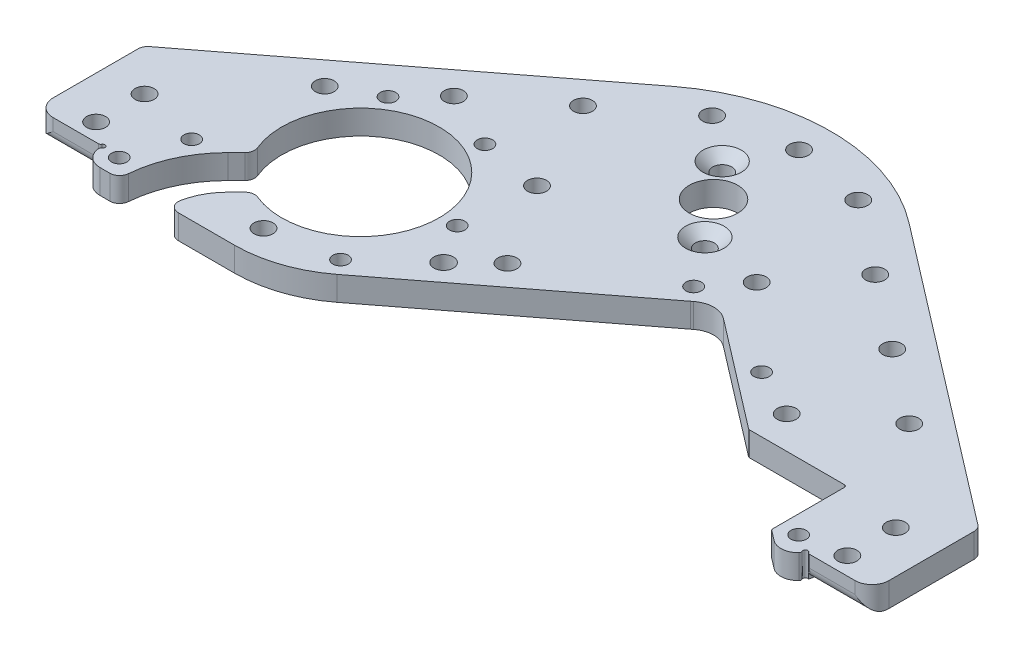
SolidWorks part; units mm, degrees
material "Alum Plate"
ref_plane "Front Plane" through (0, 0, 0) normal (0, 0, 1) x (1, 0, 0)
ref_plane "Top Plane" through (0, 0, 0) normal (0, 1, 0) x (1, 0, 0)
ref_plane "Right Plane" through (0, 0, 0) normal (1, 0, 0) x (0, 0, -1)
sketch "Top Layout" plane through (0, 0, 0) normal (0, 1, 0) x (1, 0, 0)
  line L0 (-114.046, -123.825) -> (-104.775, -123.825) construction
  line L1 (-104.775, -142.875) -> (-101.6, -142.875)
  line L2 (-104.775, -142.875) -> (-104.775, -104.775)
  line L3 (-104.775, -104.775) -> (-101.6, -104.775)
  line L4 (-101.6, -142.875) -> (-101.6, -104.775)
  line L5 (-104.775, -142.875) -> (-101.6, -104.775) construction
  line L6 (-104.775, -104.775) -> (-101.6, -142.875) construction
  line L7 (-19.05, -105.8164) -> (-101.6, -105.8164)
  line L8 (-19.05, -105.8164) -> (-19.05, -141.8336)
  line L9 (-19.05, -141.8336) -> (-101.6, -141.8336)
  line L10 (-101.6, -105.8164) -> (-101.6, -141.8336)
  line L11 (-19.05, -105.8164) -> (-101.6, -141.8336) construction
  line L12 (-19.05, -141.8336) -> (-101.6, -105.8164) construction
  line L13 (-133.096, -85.725) -> (-114.046, -85.725)
  line L14 (-133.096, -85.725) -> (-133.096, -161.925)
  line L15 (-133.096, -161.925) -> (-114.046, -161.925)
  line L16 (-114.046, -85.725) -> (-114.046, -161.925)
  line L17 (-133.096, -85.725) -> (-114.046, -161.925) construction
  line L18 (-133.096, -161.925) -> (-114.046, -85.725) construction
  line L19 (-104.775, -123.825) -> (0, -123.825) construction
  line L20 (0, -123.825) -> (0, 0) construction
  line L21 (-52.3528, -40.1717) -> (0, 0) construction
  line L22 (-70.6449, -16.3328) -> (-18.2922, 23.8388)
  line L23 (-34.0606, -64.0105) -> (18.2922, -23.8388)
  line L24 (-30.9251, 40.3023) -> (-122.2248, -29.7544)
  line L25 (-153.9748, -53.975) -> (-153.9748, -123.825)
  line L26 (-109.5248, -162.052) -> (109.5248, -162.052)
  line L27 (0, -162.052) -> (0, -123.825) construction
  line L28 (-109.5248, -162.052) -> (-109.5248, -20.0093) construction
  line L29 (-104.775, -142.875) -> (-104.775, -152.527)
  line L30 (-104.775, -152.527) -> (104.775, -152.527)
  line L31 (104.775, -104.775) -> (101.6, -104.775)
  line L32 (-144.4498, -73.025) -> (-109.5248, -73.025)
  line L33 (-144.4498, -73.025) -> (-144.4498, -123.825)
  line L34 (-144.4498, -123.825) -> (-109.5248, -123.825) construction
  line L35 (-109.5248, -73.025) -> (-109.5248, -162.052)
  line L36 (-144.4498, -73.025) -> (-109.5248, -123.825) construction
  line L37 (-144.4498, -123.825) -> (-109.5248, -73.025) construction
  line L38 (101.6, -142.875) -> (101.6, -104.775)
  line L39 (104.775, -142.875) -> (101.6, -142.875)
  line L40 (104.775, -142.875) -> (104.775, -104.775)
  line L41 (104.775, -142.875) -> (104.775, -152.527)
  line L42 (109.5248, -162.052) -> (109.5248, -20.0093) construction
  line L43 (30.9251, 40.3023) -> (122.2248, -29.7544)
  line L45 (19.05, -141.8336) -> (101.6, -141.8336)
  line L46 (101.6, -105.8164) -> (101.6, -141.8336)
  line L47 (19.05, -105.8164) -> (101.6, -105.8164)
  line L48 (19.05, -105.8164) -> (19.05, -141.8336)
  line L49 (133.096, -161.925) -> (114.046, -161.925)
  line L50 (114.046, -85.725) -> (114.046, -161.925)
  line L51 (133.096, -85.725) -> (114.046, -85.725)
  line L52 (133.096, -85.725) -> (133.096, -161.925)
  line L53 (144.4498, -123.825) -> (109.5248, -123.825) construction
  line L54 (109.5248, -73.025) -> (109.5248, -162.052)
  line L55 (144.4498, -73.025) -> (109.5248, -73.025)
  line L56 (144.4498, -73.025) -> (144.4498, -123.825)
  line L57 (-109.5248, -123.825) -> (-109.5248, -162.052) construction
  line L62 (-153.9748, -53.975) -> (-122.2248, -53.975)
  line L63 (-122.2248, -53.975) -> (-122.2248, -29.7544)
  line L64 (-144.4498, -123.825) -> (-153.9748, -123.825)
  line L65 (153.9748, -53.975) -> (153.9748, -123.825)
  line L66 (109.5248, -123.825) -> (109.5248, -162.052) construction
  line L67 (144.4498, -123.825) -> (153.9748, -123.825)
  line L68 (122.2248, -29.7544) -> (122.2248, -53.975)
  line L73 (-104.775, -104.775) -> (-104.775, -16.3647) construction
  line L74 (-95.25, -162.052) -> (-95.25, -9.0559) construction
  line L75 (-109.5248, -162.052) -> (-109.5248, -123.825) construction
  line L76 (109.5248, -162.052) -> (109.5248, -123.825) construction
  line L77 (122.2248, -53.975) -> (153.9748, -53.975)
  line L83 (104.775, -155.5496) -> (-104.775, -155.5496) construction
  line L88 (95.25, -162.052) -> (95.25, -9.0559) construction
  line L89 (104.775, -104.775) -> (104.775, -16.3647) construction
  line L92 (-104.775, -152.527) -> (-104.775, -162.052) construction
  line L93 (-14.605, -76.327) -> (14.605, -76.327)
  line L94 (-14.605, -76.327) -> (-14.605, -152.527)
  line L95 (-14.605, -152.527) -> (14.605, -152.527)
  line L96 (14.605, -76.327) -> (14.605, -152.527)
  line L97 (-14.605, -76.327) -> (14.605, -152.527) construction
  line L98 (-14.605, -152.527) -> (14.605, -76.327) construction
  line L99 (104.775, -152.527) -> (104.775, -162.052) construction
  line L100 (-19.05, -105.8164) -> (0, -105.8164) construction
  line L107 (0, -105.8164) -> (19.05, -105.8164) construction
  line L108 (104.775, -123.825) -> (114.046, -123.825) construction
  circle A0 centre (0, 0) radius 114.3
  circle A1 centre (0, 0) radius 6.35
  circle A2 centre (-52.3528, -40.1717) radius 17.8
  circle A3 centre (0, 0) radius 30.0482
  circle A4 centre (-52.3528, -40.1717) radius 30.0482
  arc A5 (-30.9251, 40.3023) -> (30.9251, 40.3023) centre (0, 0) cw
  point P2 (-103.1875, -123.825)
  point P7 (-60.325, -123.825)
  point P12 (-123.571, -123.825)
  point P30 (-126.9873, -98.425)
  point P35 (0, -114.427)
  point P53 (0, -152.527)
  dimension "D1" = 35.6
  dimension "D2" = 12.7
  dimension "D3" = 228.6
  dimension "D11" = 60.0964
  dimension "D12" = 50.8
  dimension "D14" = 52.5
  dimension "D4" = 3.175
  dimension "D5" = 19.05
  dimension "D6" = 76.2
  dimension "D7" = 82.55
  dimension "D8" = 38.1
  dimension "D9" = 104.775
  dimension "D10" = 18.0086
  dimension "D13" = 9.525
  dimension "D15" = 4.7498
  dimension "D16" = 9.525
  dimension "D17" = 9.652
  dimension "D18" = 50.8
  dimension "D19" = 12.446
  dimension "D20" = 65.9892
  dimension "D21" = 19.05
  dimension "D22" = 34.925
  dimension "D23" = 123.825
  dimension "D24" = 12.7
  dimension "D25" = 9.525
  dimension "D26" = 29.21
  dimension "D27" = 76.2
  dimension "D28" = 3.0226
sketch "Side Layout" plane through (0, 0, 0) normal (1, 0, 0) x (0, 0, -1)
  line L0 (0, -38.1) -> (0, 33.7344) construction
  line L1 (-114.3, -20.955) -> (114.3, -20.955)
  line L2 (-114.3, -20.955) -> (-114.3, -33.655)
  line L3 (-114.3, -33.655) -> (114.3, -33.655)
  line L4 (114.3, -20.955) -> (114.3, -33.655)
  line L5 (-114.3, -20.955) -> (114.3, -33.655) construction
  line L6 (-114.3, -33.655) -> (114.3, -20.955) construction
  line L7 (-9.525, -32.9406) -> (9.525, -32.9406)
  line L8 (-9.525, -32.9406) -> (-9.525, -38.1)
  line L9 (-9.525, -38.1) -> (9.525, -38.1)
  line L10 (9.525, -32.9406) -> (9.525, -38.1)
  line L11 (-9.525, -32.9406) -> (9.525, -38.1) construction
  line L12 (-9.525, -38.1) -> (9.525, -32.9406) construction
  line L13 (-11.9126, -29.3338) -> (11.9126, -29.3338)
  line L14 (-11.9126, -29.3338) -> (-11.9126, -32.9406)
  line L15 (-11.9126, -32.9406) -> (11.9126, -32.9406)
  line L16 (11.9126, -29.3338) -> (11.9126, -32.9406)
  line L17 (-11.9126, -29.3338) -> (11.9126, -32.9406) construction
  line L18 (-11.9126, -32.9406) -> (11.9126, -29.3338) construction
  line L19 (-6.35, -32.9406) -> (6.35, -32.9406)
  line L20 (-6.35, -32.9406) -> (-6.35, 33.7344)
  line L21 (-6.35, 33.7344) -> (6.35, 33.7344)
  line L22 (6.35, -32.9406) -> (6.35, 33.7344)
  line L23 (-6.35, -32.9406) -> (6.35, 33.7344) construction
  line L24 (-6.35, 33.7344) -> (6.35, -32.9406) construction
  line L25 (-162.052, 0) -> (-123.825, 0) construction
  line L26 (114.3, -33.655) -> (114.3, 0) construction
  line L27 (-142.875, 19.05) -> (-104.775, 19.05)
  line L28 (-40.1717, -9.525) -> (-40.1717, 5.4) construction
  line L29 (-142.875, 19.05) -> (-142.875, -19.05)
  line L30 (-142.875, -19.05) -> (-104.775, -19.05)
  line L31 (-104.775, 19.05) -> (-104.775, -19.05)
  line L32 (-142.875, 19.05) -> (-104.775, -19.05) construction
  line L33 (-142.875, -19.05) -> (-104.775, 19.05) construction
  line L34 (-130.175, -38.1) -> (-117.9516, -38.1) construction
  line L35 (-57.9717, -14.6) -> (-22.3717, -14.6)
  line L36 (-30.0482, -2.794) -> (30.0482, -2.794)
  line L37 (-30.0482, -2.794) -> (-30.0482, -20.955)
  line L38 (-30.0482, -20.955) -> (30.0482, -20.955)
  line L39 (30.0482, -2.794) -> (30.0482, -20.955)
  line L40 (-30.0482, -2.794) -> (30.0482, -20.955) construction
  line L41 (-30.0482, -20.955) -> (30.0482, -2.794) construction
  line L42 (-30.0482, -2.794) -> (-30.0482, 0) construction
  line L43 (-123.825, 0) -> (0, 0) construction
  line L44 (-57.9717, -14.6) -> (-57.9717, 25.4)
  line L45 (-57.9717, 25.4) -> (-22.3717, 25.4)
  line L46 (-22.3717, -14.6) -> (-22.3717, 25.4)
  line L47 (-19.05, 0) -> (19.05, 0)
  line L48 (-19.05, 0) -> (-19.05, -1.9812)
  line L49 (-19.05, -1.9812) -> (19.05, -1.9812)
  line L50 (19.05, 0) -> (19.05, -1.9812)
  line L51 (-19.05, 0) -> (19.05, -1.9812) construction
  line L52 (-19.05, -1.9812) -> (19.05, 0) construction
  line L53 (-70.2199, -3.175) -> (-10.1235, -3.175)
  line L54 (-70.2199, -3.175) -> (-70.2199, -15.875)
  line L55 (-70.2199, -15.875) -> (-10.1235, -15.875)
  line L56 (-10.1235, -3.175) -> (-10.1235, -15.875)
  line L57 (-70.2199, -3.175) -> (-10.1235, -15.875) construction
  line L58 (-70.2199, -15.875) -> (-10.1235, -3.175) construction
  line L59 (-40.1717, -9.525) -> (-40.1717, 0) construction
  line L60 (-57.9717, -14.6) -> (-22.3717, 25.4) construction
  line L61 (-57.9717, 25.4) -> (-22.3717, -14.6) construction
  line L62 (-22.3717, 0) -> (-57.9717, 0) construction
  line L63 (-137.8162, 0) -> (-123.825, -13.9912) construction
  line L64 (-139.065, 15.24) -> (-108.585, 15.24) construction
  line L65 (-139.065, 15.24) -> (-139.065, -15.24) construction
  line L66 (-139.065, -15.24) -> (-108.585, -15.24) construction
  line L67 (-108.585, 15.24) -> (-108.585, -15.24) construction
  line L68 (-139.065, 15.24) -> (-108.585, -15.24) construction
  line L69 (-139.065, -15.24) -> (-108.585, 15.24) construction
  line L70 (-137.8162, 0) -> (-123.825, 13.9912) construction
  line L71 (-123.825, -13.9912) -> (-109.8338, 0) construction
  line L72 (-123.825, 13.9912) -> (-109.8338, 0) construction
  line L73 (-137.8162, 0) -> (-109.8338, 0) construction
  line L74 (-123.825, -13.9912) -> (-123.825, 13.9912) construction
  line L75 (-6.35, 17.8594) -> (6.35, 17.8594)
  line L76 (114.3, 0) -> (-114.3, 0) construction
  line L77 (-22.3717, 19.05) -> (-6.35, 19.05) construction
  line L78 (-123.825, 38.1) -> (-97.9206, 38.1) construction
  line L79 (-19.05, -3.5814) -> (19.05, -3.5814)
  line L80 (-19.05, -3.5814) -> (-19.05, -1.9812)
  line L81 (-19.05, -1.9812) -> (19.05, -1.9812)
  line L82 (19.05, -3.5814) -> (19.05, -1.9812)
  line L83 (-19.05, -3.5814) -> (19.05, -1.9812) construction
  line L84 (-19.05, -1.9812) -> (19.05, -3.5814) construction
  line L85 (-8.7376, -16.7608) -> (8.7376, -16.7608)
  line L86 (-8.7376, -16.7608) -> (-8.7376, -29.3338)
  line L87 (-8.7376, -29.3338) -> (8.7376, -29.3338)
  line L88 (8.7376, -16.7608) -> (8.7376, -29.3338)
  line L89 (-8.7376, -16.7608) -> (8.7376, -29.3338) construction
  line L90 (-8.7376, -29.3338) -> (8.7376, -16.7608) construction
  line L91 (-8.7376, -3.5814) -> (8.7376, -3.5814)
  line L92 (-8.7376, -3.5814) -> (-8.7376, -16.1544)
  line L93 (-8.7376, -16.1544) -> (8.7376, -16.1544)
  line L94 (8.7376, -3.5814) -> (8.7376, -16.1544)
  line L95 (-8.7376, -3.5814) -> (8.7376, -16.1544) construction
  line L96 (-8.7376, -16.1544) -> (8.7376, -3.5814) construction
  circle A0 centre (-123.825, 0) radius 18.0086
  circle A1 centre (-123.825, 0) radius 38.1
  circle A2 centre (-139.065, 15.24) radius 1.905
  circle A3 centre (-108.585, 15.24) radius 1.905
  circle A4 centre (-108.585, -15.24) radius 1.905
  circle A5 centre (-139.065, -15.24) radius 1.905
  circle A6 centre (-137.8162, 0) radius 1.6002
  circle A7 centre (-123.825, 13.9912) radius 1.6002
  circle A8 centre (-109.8338, 0) radius 1.6002
  circle A9 centre (-123.825, -13.9912) radius 1.6002
  point P0 (0, -27.305)
  point P6 (0, -31.1372)
  point P7 (0, -35.5203)
  point P21 (0, 0.3969)
  point P32 (0, -11.8745)
  point P43 (0, -0.9906)
  point P55 (-40.1717, -9.525)
  point P72 (-40.1717, 5.4)
  point P88 (0, -23.0473)
  point P93 (0, -2.7813)
  point P102 (0, -9.8679)
  dimension "D17" = 3.81
  dimension "D18" = 3.2004
  dimension "D1" = 12.7
  dimension "D2" = 5.1594
  dimension "D3" = 19.05
  dimension "D4" = 3.6068
  dimension "D5" = 23.8252
  dimension "D6" = 12.7
  dimension "D7" = 18.161
  dimension "D8" = 1.9812
  dimension "D9" = 12.7
  dimension "D10" = 40
  dimension "D11" = 25.4
  dimension "D12" = 50.8
  dimension "D13" = 41.275
  dimension "D14" = 30.48
  dimension "D15" = 4.445
  dimension "D16" = 19.7866
  dimension "D19" = 15.875
  dimension "D20" = 6.35
  dimension "D21" = 38.1
  dimension "D22" = 1.6002
  dimension "D23" = 38.1
  dimension "D24" = 17.4752
  dimension "D25" = 12.573
ref_plane "Plane1" through (0, 25.4, 0) normal (0, 1, 0) x (1, 0, 0)
sketch "Sketch3" plane through (0, 25.4, 0) normal (0, 1, 0) x (1, 0, 0)
  line L0 (-104.775, -36.3747) -> (-30.9251, 20.2924)
  line L1 (-104.775, -104.775) -> (-104.775, -16.3647) construction
  line L2 (0, -200130.175) -> (0, 199882.0484) construction
  line L3 (-30.9251, 40.3023) -> (-122.2248, -29.7544) construction
  line L5 (-104.775, -36.3747) -> (-104.775, -77.6497)
  line L6 (-92.075, -77.6497) -> (-104.775, -77.6497)
  line L7 (30.9251, 20.2924) -> (104.775, -36.3747)
  line L8 (104.775, -77.6497) -> (92.075, -77.6497)
  line L9 (104.775, -36.3747) -> (104.775, -77.6497)
  line L11 (104.775, -104.775) -> (104.775, -16.3647) construction
  line L12 (30.9251, 40.3023) -> (122.2248, -29.7544) construction
  line L13 (92.075, -74.6536) -> (24.1423, -22.5271)
  line L14 (-32.2514, -66.3682) -> (20.1013, -26.1965)
  line L15 (-30.9251, 20.2924) -> (0, 44.022)
  line L16 (0, 44.022) -> (30.9251, 20.2924)
  line L17 (-92.075, -77.6497) -> (-92.075, -73.1917)
  line L19 (-92.075, -73.1917) -> (-52.3528, -73.1917)
  line L20 (92.075, -74.6536) -> (92.075, -77.6497)
  circle A1 centre (-52.3528, -40.1717) radius 20.6375
  circle A2 centre (0, 0) radius 6.35
  circle A3 centre (0, 0) radius 6.35 construction
  arc A4 (-52.3528, -73.1917) -> (-32.2514, -66.3682) centre (-52.3528, -40.1717) ccw
  arc A5 (20.1013, -26.1965) -> (24.1423, -22.5271) centre (0, 0) ccw
  arc A6 (30.9251, 20.2924) -> (-30.9251, 20.2924) centre (0, -20.01) ccw construction
  point P28 (0, 44.022)
  dimension "D1" = 33.02
  dimension "D5" = 50.8
  dimension "D7" = 41.275
  dimension "D2" = 41.275
  dimension "D3" = 34.925
  dimension "D4" = 12.7
  dimension "D6" = 38.1
extrude "Boss-Extrude1" add sketch "Sketch3" against normal blind 6.35
ref_plane "Plane3" through (-104.775, 0, 0) normal (-1, 0, 0) x (0, 0, 1)
sketch "Sketch6" plane through (-104.775, 0, 0) normal (-1, 0, 0) x (0, 0, 1)
  line L0 (162.052, -25.4) -> (162.052, 25.4)
  line L1 (162.052, 25.4) -> (77.6497, 25.4)
  line L2 (36.3747, 25.4) -> (77.6497, 25.4) construction
  line L3 (147.7645, 11.1125) -> (162.052, 11.1125) construction
  line L4 (162.052, 0) -> (71.2997, 0) construction
  line L5 (77.6497, 25.4) -> (77.6497, 19.05)
  line L6 (77.6497, 19.05) -> (36.3747, 19.05)
  line L7 (36.3747, 19.05) -> (36.3747, 6.35)
  line L8 (36.3747, 6.35) -> (71.2997, 6.35)
  line L10 (99.6315, -3.175) -> (99.6315, 11.1125) construction
  line L11 (71.2997, -25.4) -> (162.052, -25.4)
  line L13 (71.2997, 6.35) -> (71.2997, -25.4)
  line L14 (152.527, -25.4) -> (152.527, 25.4) construction
  line L15 (99.6315, 11.1125) -> (99.6315, 25.4) construction
  line L16 (147.7645, 11.1125) -> (147.7645, 25.4) construction
  line L17 (94.869, -7.9375) -> (104.394, -7.9375) construction
  line L18 (94.869, -7.9375) -> (94.869, 25.4) construction
  line L19 (94.869, 25.4) -> (104.394, 25.4) construction
  line L20 (104.394, -7.9375) -> (104.394, 25.4) construction
  line L21 (94.869, -7.9375) -> (104.394, 25.4) construction
  line L22 (94.869, 25.4) -> (104.394, -7.9375) construction
  line L23 (147.7645, 11.1125) -> (147.7645, -3.175) construction
  line L24 (104.394, -7.9375) -> (123.825, -7.9375) construction
  line L25 (143.002, -7.9375) -> (152.527, -7.9375) construction
  line L26 (143.002, -7.9375) -> (143.002, 25.4) construction
  line L27 (143.002, 25.4) -> (152.527, 25.4) construction
  line L28 (152.527, -7.9375) -> (152.527, 25.4) construction
  line L29 (143.002, -7.9375) -> (152.527, 25.4) construction
  line L30 (143.002, 25.4) -> (152.527, -7.9375) construction
  line L31 (123.825, -7.9375) -> (152.527, -7.9375) construction
  line L32 (104.775, 19.05) -> (104.775, -19.05) construction
  line L34 (155.702, -25.4) -> (155.702, 25.4) construction
  circle A0 centre (109.8338, 0) radius 1.6002 construction
  circle A1 centre (123.825, 13.9912) radius 1.6002 construction
  circle A2 centre (137.8162, 0) radius 1.6002 construction
  circle A3 centre (123.825, -13.9912) radius 1.6002 construction
  circle A4 centre (109.8338, 0) radius 1.6002 construction
  circle A5 centre (123.825, 13.9912) radius 1.6002 construction
  circle A6 centre (137.8162, 0) radius 1.6002 construction
  circle A7 centre (123.825, -13.9912) radius 1.6002 construction
  circle A8 centre (123.825, 0) radius 18.0086 construction
  circle A9 centre (123.825, 0) radius 18.0086 construction
  circle A10 centre (123.825, 0) radius 9.525
  circle A11 centre (108.585, -15.24) radius 1.905 construction
  circle A12 centre (108.585, 15.24) radius 1.905 construction
  circle A13 centre (139.065, 15.24) radius 1.905 construction
  circle A14 centre (139.065, -15.24) radius 1.905 construction
  circle A15 centre (108.585, -15.24) radius 1.905
  circle A16 centre (108.585, 15.24) radius 1.905
  circle A17 centre (139.065, 15.24) radius 1.905
  circle A18 centre (139.065, -15.24) radius 1.905
  circle A19 centre (147.7645, 11.1125) radius 2.5527
  circle A26 centre (99.6315, 11.1125) radius 2.5527
  circle A27 centre (99.6315, -3.175) radius 2.5527
  circle A28 centre (147.7645, -3.175) radius 2.5527
  point P29 (0, 0)
  point P55 (99.6315, 8.7312)
  point P61 (147.7645, 8.7312)
  dimension "D4" = 19.05
  dimension "D7" = 5.1054
  dimension "D1" = 6.35
  dimension "D2" = 12.7
  dimension "D3" = 25.4
  dimension "D5" = 6.35
  dimension "D6" = 3.175
  dimension "D8" = 0.381
  dimension "D9" = 14.2875
  dimension "D10" = 9.525
  dimension "D12" = 33.3375
sketch "Sketch12" [suppressed] plane through (0, 19.05, 0) normal (0, 1, 0) x (1, 0, 0)
  line L0 (-104.775, -77.6497) -> (-104.775, -36.3747)
  line L1 (-104.775, -36.3747) -> (-92.075, -36.3747)
  line L3 (-92.075, -36.3747) -> (-92.075, -77.6497)
  line L5 (-92.075, -77.6497) -> (-104.775, -77.6497)
  line L6 (-98.425, -77.6497) -> (-98.425, -63.3622) construction
  line L7 (-98.425, -63.3622) -> (-98.425, -50.6622) construction
  line L8 (-98.425, -50.6622) -> (-98.425, -36.3747) construction
  line L10 (-98.425, -36.3747) -> (-104.775, -36.3747) construction
  circle A0 centre (-98.425, -63.3622) radius 2.5527
  circle A1 centre (-98.425, -50.6622) radius 2.5527
  dimension "D2" = 5.1054
  dimension "D1" = 12.7
  dimension "D3" = 12.7
sketch "Sketch8" plane through (0, 25.4, 0) normal (0, 1, 0) x (1, 0, 0)
  line L0 (-109.5248, -162.052) -> (-109.5248, -20.0093) construction
  line L1 (-104.775, -77.6497) -> (-109.5248, -77.6497)
  line L2 (-104.775, -77.6497) -> (-104.775, -36.3747)
  line L3 (-104.775, -36.3747) -> (-109.5248, -36.3747)
  line L4 (-109.5248, -77.6497) -> (-109.5248, -36.3747)
  line L5 (-104.775, -77.6497) -> (-109.5248, -36.3747) construction
  line L6 (-104.775, -36.3747) -> (-109.5248, -77.6497) construction
  line L7 (104.775, -77.6497) -> (109.5248, -77.6497)
  line L8 (104.775, -77.6497) -> (104.775, -36.3747)
  line L9 (104.775, -36.3747) -> (109.5248, -36.3747)
  line L10 (109.5248, -77.6497) -> (109.5248, -36.3747)
  line L11 (104.775, -77.6497) -> (109.5248, -36.3747) construction
  line L12 (104.775, -36.3747) -> (109.5248, -77.6497) construction
  point P4 (-107.1499, -57.0122)
  point P10 (107.1499, -57.0122)
extrude "Boss-Extrude4" add sketch "Sketch8" against normal through all
sketch "Sketch9" plane through (0, 25.4, 0) normal (0, 1, 0) x (1, 0, 0)
  line L0 (7.4916, -9.7632) -> (0, 0) construction
  line L1 (0, 0) -> (-7.4916, 9.7632) construction
  line L2 (0, 44.022) -> (-104.775, -36.3747) construction
  circle A0 centre (-7.4916, 9.7632) radius 2.4892
  circle A1 centre (7.4916, -9.7632) radius 2.4892
  dimension "D2" = 4.9784
  dimension "D1" = 24.6126
extrude "Collar Holes" cut sketch "Sketch9" against normal through all
sketch "Sketch10" plane through (0, 25.4, 0) normal (0, 1, 0) x (1, 0, 0)
  line L0 (0, 33.4567) -> (0, 30.79) construction
  line L1 (-5.1026, 40.1066) -> (0, 33.4567) construction
  line L2 (0, 33.4567) -> (5.1026, 40.1066) construction
  line L3 (0, 44.022) -> (-104.775, -36.3747) construction
  line L4 (104.775, -36.3747) -> (0, 44.022) construction
  circle A0 centre (0, 33.4567) radius 4.7625 construction
  circle A1 centre (0, 33.4567) radius 2.0193
  arc A3 (30.9251, 20.2924) -> (-30.9251, 20.2924) centre (0, -20.01) ccw construction
  dimension "D2" = 9.525
  dimension "D3" = 4.0386
  dimension "D1" = 8.382
extrude "Spacer Holes" cut sketch "Sketch10" against normal through all
pattern_linear "Spacer Hole Pattern" count 5 spacing 24.13 along (-0.7934, 0, 0.6088) of "Spacer Holes"
mirror "Spacer Hole Mirror" about plane through (0, 0, 0) normal (1, 0, 0) of "Spacer Hole Pattern"
sketch "Sketch16" plane through (0, 25.4, 0) normal (0, 1, 0) x (1, 0, 0)
  line L0 (-109.5248, -50.6622) -> (-98.425, -50.6622) construction
  line L1 (-109.5248, -36.3747) -> (-109.5248, -77.6497) construction
  line L2 (-98.425, -50.6622) -> (-98.425, -63.3622) construction
  line L3 (-98.425, -63.3622) -> (-109.5248, -63.3622) construction
  line L4 (-98.425, -63.3622) -> (-98.425, -77.6497) construction
  line L5 (-109.5248, -77.6497) -> (-92.075, -77.6497) construction
  line L6 (-98.425, -50.6622) -> (-98.425, -36.3747) construction
  line L7 (-104.775, -36.3747) -> (-109.5248, -36.3747) construction
  line L8 (-104.775, -36.3747) -> (-104.775, -77.6497) construction
  line L9 (0, 0) -> (0, 30.79) construction
  line L10 (104.775, -36.3747) -> (104.775, -77.6497) construction
  circle A0 centre (-98.425, -50.6622) radius 2.0193
  circle A1 centre (-98.425, -63.3622) radius 2.0193
  circle A4 centre (98.425, -63.3622) radius 2.0193
  circle A5 centre (98.425, -50.6622) radius 2.0193
  arc A6 (30.9251, 20.2924) -> (-30.9251, 20.2924) centre (0, -20.01) ccw construction
  dimension "D1" = 4.0386
  dimension "D2" = 12.7
  dimension "D3" = 6.35
extrude "Custom Nutstrip Holes" cut sketch "Sketch16" against normal through all
sketch "Sketch36" plane through (0, 25.4, 0) normal (0, 1, 0) x (1, 0, 0)
  line L0 (-52.3528, -65.5717) -> (-12.44, -41.5615) construction
  line L1 (-12.44, -41.5615) -> (24.5129, -13.2066) construction
  line L2 (24.5129, -13.2066) -> (58.2939, -39.1277) construction
  line L3 (-32.2514, -66.3682) -> (20.1013, -26.1965) construction
  line L4 (24.1423, -22.5271) -> (92.075, -74.6536) construction
  line L5 (-12.44, -41.5615) -> (-7.8012, -47.6069) construction
  line L6 (58.2939, -39.1277) -> (53.6552, -45.1731) construction
  line L7 (-52.3528, -65.5717) -> (-52.3528, -40.1717) construction
  line L8 (58.2939, -39.1277) -> (92.075, -65.0488) construction
  line L9 (92.075, -65.0488) -> (92.075, -77.6497) construction
  line L10 (-52.3528, -40.1717) -> (-26.1764, -20.0858) construction
  line L11 (-26.1764, -20.0858) -> (0, 0) construction
  line L12 (92.075, -74.6536) -> (92.075, -77.6497) construction
  circle A0 centre (-52.3528, -65.5717) radius 2.0193
  circle A1 centre (58.2939, -39.1277) radius 2.0193
  circle A2 centre (24.5129, -13.2066) radius 2.0193
  circle A3 centre (-12.44, -41.5615) radius 2.0193
  circle A4 centre (-76.5745, -25.3009) radius 2.0193 construction
  circle A5 centre (-52.3528, -65.5717) radius 4.7625 construction
  circle A6 centre (-12.44, -41.5615) radius 4.7625 construction
  circle A7 centre (24.5129, -13.2066) radius 4.7625 construction
  circle A8 centre (58.2939, -39.1277) radius 4.7625 construction
  arc A9 (-52.3528, -73.1917) -> (-32.2514, -66.3682) centre (-52.3528, -40.1717) ccw construction
  circle A10 centre (-26.1764, -20.0858) radius 2.0193
  dimension "D1" = 9.525
  dimension "D2" = 25.4
  dimension "D3" = 7.62
extrude "Aux Spacer Holes" cut sketch "Sketch36" against normal through all
sketch "Sketch38" [suppressed] plane through (-104.775, 0, 0) normal (-1, 0, 0) x (0, 0, 1)
  line L1 (152.527, -7.9375) -> (143.002, -7.9375)
  line L2 (152.527, -7.9375) -> (152.527, 25.4)
  line L3 (152.527, 25.4) -> (143.002, 25.4)
  line L4 (143.002, -7.9375) -> (143.002, 25.4)
  line L5 (152.527, -7.9375) -> (143.002, 25.4) construction
  line L6 (152.527, 25.4) -> (143.002, -7.9375) construction
  point P4 (147.7645, 8.7312)
extrude "Cut-Extrude16" [suppressed] cut sketch "Sketch38" against normal blind 9.525
sketch "Sketch46" [suppressed] plane through (-104.775, 0, 0) normal (-1, 0, 0) x (0, 0, 1)
  line L0 (142.875, 19.05) -> (104.775, -19.05) construction
  line L1 (104.14, 19.685) -> (143.51, 19.685)
  line L2 (104.14, 19.685) -> (104.14, -19.685)
  line L3 (104.14, -19.685) -> (143.51, -19.685)
  line L4 (143.51, 19.685) -> (143.51, -19.685)
  line L5 (104.14, 19.685) -> (143.51, -19.685) construction
  line L6 (104.14, -19.685) -> (143.51, 19.685) construction
  point P0 (123.825, 0)
  dimension "D1" = 39.37
extrude "Cut-Extrude21" [suppressed] cut sketch "Sketch46" against normal blind 6.985
ref_plane "Plane5" through (0, 0, 152.527) normal (0, 0, 1) x (1, 0, 0)
sketch "Sketch41" plane through (0, 0, 152.527) normal (0, 0, 1) x (1, 0, 0)
  line L0 (-104.775, -7.9375) -> (-104.775, 25.4) construction
  line L1 (-104.775, -7.9375) -> (-104.775, 12.7)
  line L2 (-104.775, -7.9375) -> (104.775, -7.9375)
  line L3 (104.775, -7.9375) -> (104.775, 12.7)
  line L4 (104.775, 25.4) -> (-104.775, 25.4)
  line L5 (0, -7.9375) -> (0, 25.4) construction
  line L6 (-104.775, 3.9624) -> (-100.0125, 3.9624) construction
  line L7 (-100.0125, 3.9624) -> (-100.0125, 25.4) construction
  line L8 (104.775, 3.9624) -> (100.0125, 3.9624) construction
  line L9 (100.0125, 3.9624) -> (100.0125, 25.4) construction
  line L10 (19.05, 20.6375) -> (23.8252, 20.6375) construction
  line L11 (19.05, 15.875) -> (78.5876, 15.875) construction
  line L12 (19.05, 15.875) -> (19.05, 25.4) construction
  line L13 (19.05, 25.4) -> (78.5876, 25.4) construction
  line L14 (78.5876, 15.875) -> (78.5876, 25.4) construction
  line L15 (19.05, 15.875) -> (78.5876, 25.4) construction
  line L16 (19.05, 25.4) -> (78.5876, 15.875) construction
  line L17 (23.8252, 20.6375) -> (38.1127, 20.6375) construction
  line L18 (38.1127, 20.6375) -> (52.4002, 20.6375) construction
  line L19 (52.4002, 20.6375) -> (66.6877, 20.6375) construction
  line L20 (-104.775, 25.4) -> (-112.395, 25.4)
  line L21 (-112.395, 25.4) -> (-112.395, 3.175)
  line L22 (-112.395, 3.175) -> (-109.5248, 3.175)
  line L23 (-109.5248, 3.175) -> (-109.5248, 12.7)
  line L24 (-109.5248, 12.7) -> (-104.775, 12.7)
  line L25 (-104.775, 12.7) -> (-104.775, 25.4) construction
  line L26 (104.775, 25.4) -> (112.395, 25.4)
  line L27 (112.395, 25.4) -> (112.395, 3.175)
  line L28 (112.395, 3.175) -> (109.5248, 3.175)
  line L29 (109.5248, 3.175) -> (109.5248, 12.7)
  line L30 (109.5248, 12.7) -> (104.775, 12.7)
  line L31 (104.775, 12.7) -> (104.775, 25.4) construction
  line L32 (-100.0125, 3.9624) -> (-87.3125, 3.9624) construction
  line L33 (-63.5, -1.5875) -> (0, -1.5875) construction
  line L34 (0, -1.5875) -> (63.5, -1.5875) construction
  line L35 (63.5, -1.5875) -> (63.5, -7.9375) construction
  circle A0 centre (-100.0125, 3.9624) radius 2.5527
  circle A1 centre (100.0125, 3.9624) radius 2.5527
  circle A2 centre (23.8252, 20.6375) radius 2.5527
  circle A3 centre (38.1127, 20.6375) radius 2.5527
  circle A4 centre (52.4002, 20.6375) radius 2.5527
  circle A5 centre (66.6877, 20.6375) radius 2.5527
  circle A6 centre (-66.6877, 20.6375) radius 2.5527
  circle A7 centre (-52.4002, 20.6375) radius 2.5527
  circle A8 centre (-38.1127, 20.6375) radius 2.5527
  circle A9 centre (-23.8252, 20.6375) radius 2.5527
  circle A10 centre (-87.3125, 3.9624) radius 2.5527
  circle A11 centre (87.3125, 3.9624) radius 2.5527
  circle A12 centre (-63.5, -1.5875) radius 2.5527
  circle A13 centre (63.5, -1.5875) radius 2.5527
  point P14 (48.8188, 20.6375)
  dimension "D3" = 5.1054
  dimension "D7" = 5.1054
  dimension "D1" = 21.4376
  dimension "D2" = 4.7625
  dimension "D4" = 9.525
  dimension "D5" = 59.5376
  dimension "D6" = 4.7752
  dimension "D8" = 14.2875
  dimension "D9" = 7.62
  dimension "D10" = 4.7498
  dimension "D11" = 12.7
  dimension "D12" = 9.525
  dimension "D13" = 19.05
  dimension "D14" = 12.7
  dimension "D15" = 6.35
  dimension "D16" = 63.5
sketch "Sketch43" [suppressed] plane through (-109.5248, 0, 0) normal (-1, 0, 0) x (0, 0, 1)
  line L1 (152.527, 12.7) -> (155.702, 12.7)
  line L2 (152.527, 12.7) -> (152.527, 25.4)
  line L3 (152.527, 25.4) -> (155.702, 25.4)
  line L4 (155.702, 12.7) -> (155.702, 25.4)
  line L5 (152.527, 12.7) -> (155.702, 25.4) construction
  line L6 (152.527, 25.4) -> (155.702, 12.7) construction
  line L7 (162.052, 25.4) -> (77.6497, 25.4) construction
  point P4 (154.1145, 19.05)
  dimension "D1" = 3.175
sketch "Sketch44" plane through (0, 25.4, 0) normal (0, 1, 0) x (1, 0, 0)
  line L0 (73.8315, -147.7645) -> (73.8315, -152.527) construction
  line L1 (92.075, -74.6536) -> (92.075, -77.6497) construction
  line L2 (-92.075, -77.6497) -> (-92.075, -73.1917) construction
  line L3 (0, -123.825) -> (0, 0) construction
  line L4 (-92.075, -73.1917) -> (-52.3528, -73.1917) construction
  line L5 (-104.775, -104.775) -> (-104.775, -16.3647) construction
  line L6 (-32.2514, -66.3682) -> (20.1013, -26.1965) construction
  line L21 (-104.775, -68.1247) -> (-104.775, -152.527)
  line L22 (-104.775, -152.527) -> (104.775, -152.527)
  line L23 (104.775, -152.527) -> (104.775, -68.1247)
  line L34 (-104.775, -99.6315) -> (-100.0125, -99.6315) construction
  line L35 (-104.775, -147.7645) -> (-100.0125, -147.7645) construction
  line L36 (0, -152.527) -> (0, -35.6178) construction
  line L38 (30.969, -147.7645) -> (45.2565, -147.7645) construction
  line L39 (45.2565, -147.7645) -> (59.544, -147.7645) construction
  line L40 (59.544, -147.7645) -> (73.8315, -147.7645) construction
  line L41 (23.8252, -152.527) -> (30.969, -152.527) construction
  line L42 (104.775, -152.527) -> (-104.775, -152.527) construction
  line L43 (30.969, -152.527) -> (38.1127, -152.527) construction
  line L44 (30.969, -152.527) -> (30.969, -147.7645) construction
  line L45 (-92.075, -77.6497) -> (-104.775, -77.6497) construction
  line L48 (-35.1507, -62.5899) -> (-8.9743, -42.504) construction
  line L49 (-8.9743, -42.504) -> (17.2021, -22.4182) construction
  line L50 (45.5313, -32.9364) -> (87.3125, -64.9962) construction
  line L51 (92.075, -74.6536) -> (24.1423, -22.5271) construction
  line L52 (104.775, -77.6497) -> (92.075, -77.6497) construction
  line L79 (-104.775, -68.1247) -> (-92.075, -68.1247)
  line L80 (-92.075, -68.1247) -> (-92.075, -63.6667)
  line L85 (21.8118, -8.7328) -> (92.075, -62.6476)
  line L86 (-38.0499, -58.8115) -> (14.3028, -18.6398)
  line L87 (-92.075, -63.6667) -> (-52.3528, -63.6667)
  line L88 (92.075, -62.6476) -> (92.075, -68.1247)
  line L89 (92.075, -68.1247) -> (104.775, -68.1247)
  circle A0 centre (-73.8315, -147.7645) radius 2.5527
  circle A1 centre (-59.544, -147.7645) radius 2.5527
  circle A2 centre (-45.2565, -147.7645) radius 2.5527
  circle A3 centre (-30.969, -147.7645) radius 2.5527
  circle A17 centre (-100.0125, -99.6315) radius 2.5527
  circle A18 centre (-100.0125, -147.7645) radius 2.5527
  circle A19 centre (100.0125, -147.7645) radius 2.5527
  circle A20 centre (100.0125, -99.6315) radius 2.5527
  circle A21 centre (30.969, -147.7645) radius 2.5527
  circle A22 centre (45.2565, -147.7645) radius 2.5527
  circle A23 centre (59.544, -147.7645) radius 2.5527
  circle A24 centre (73.8315, -147.7645) radius 2.5527
  circle A25 centre (-87.3125, -68.4292) radius 4.7625 construction
  circle A26 centre (-35.1507, -62.5899) radius 4.7625 construction
  circle A27 centre (-8.9743, -42.504) radius 4.7625 construction
  circle A28 centre (17.2021, -22.4182) radius 4.7625 construction
  circle A29 centre (45.5313, -32.9364) radius 4.7625 construction
  circle A30 centre (87.3125, -64.9962) radius 4.7625 construction
  circle A32 centre (-87.3125, -68.4292) radius 2.5527
  circle A33 centre (-35.1507, -62.5899) radius 2.5527
  circle A34 centre (-8.9743, -42.504) radius 2.5527 construction
  circle A35 centre (17.2021, -22.4182) radius 2.5527
  circle A36 centre (45.5313, -32.9364) radius 2.5527
  circle A37 centre (87.3125, -64.9962) radius 2.5527
  circle A38 centre (-97.155, -85.2697) radius 7.62 construction
  circle A39 centre (97.155, -85.2697) radius 7.62 construction
  circle A40 centre (24.5121, -32.4156) radius 7.62 construction
  arc A41 (20.1013, -26.1965) -> (24.1423, -22.5271) centre (0, 0) ccw construction
  circle A42 centre (-97.155, -85.2697) radius 2.5527
  circle A43 centre (24.5121, -32.4156) radius 2.5527
  circle A44 centre (97.155, -85.2697) radius 2.5527
  arc A56 (14.3028, -18.6398) -> (21.8118, -8.7328) centre (0, 0) ccw
  arc A57 (-52.3528, -63.6667) -> (-38.0499, -58.8115) centre (-52.3528, -40.1717) ccw
  point P4 (-104.775, -152.527)
  dimension "D2" = 5.1054
  dimension "D7" = 5.1054
  dimension "D8" = 15.24
  dimension "D3" = 9.525
  dimension "D9" = 9.525
  dimension "D4" = 4.7625
  dimension "D5" = 14.2875
  dimension "D6" = 9.525
  dimension "D1" = 4.7625
  dimension "D10" = 52.664
sketch "Sketch82" [suppressed] plane through (0, 28.829, 0) normal (0, 1, 0) x (1, 0, 0)
  line L0 (-52.3528, -63.6667) -> (-92.075, -63.6667) construction
  line L1 (-52.3528, -65.5717) -> (-52.3528, -63.6667) construction
  line L2 (-12.4467, -41.5667) -> (-13.6064, -40.0553) construction
  line L3 (14.3028, -18.6398) -> (-38.0499, -58.8115) construction
  line L4 (24.5175, -13.2101) -> (25.6772, -11.6988) construction
  line L5 (92.075, -62.6476) -> (21.8118, -8.7328) construction
  line L6 (58.2962, -39.1295) -> (59.4559, -37.6181) construction
  line L7 (21.4643, -9.5551) -> (21.8118, -8.7328)
  line L8 (21.8118, -8.7328) -> (22.2143, -9.0416)
  circle A0 centre (-52.3528, -65.5717) radius 4.7625
  circle A1 centre (-12.4467, -41.5667) radius 4.7625
  arc A2 (21.4643, -9.5551) -> (22.2143, -9.0416) centre (24.5175, -13.2101) ccw
  circle A3 centre (58.2962, -39.1295) radius 4.7625
  arc A4 (14.3028, -18.6398) -> (21.8118, -8.7328) centre (0, 0) ccw construction
  dimension "D1" = 9.525
  dimension "D2" = 1.905
  dimension "D3" = 30.8104
  dimension "D4" = 83.6926
  dimension "D5" = 41.1154
extrude "Cut-Extrude38" [suppressed] cut sketch "Sketch82" against normal up to surface (3.429 mm away)
sketch "Sketch45" [suppressed] plane through (0, -25.4, 0) normal (0, -1, 0) x (1, 0, 0)
  circle A2 centre (24.5121, 32.4156) radius 6.35
  circle A4 centre (-97.155, 85.2697) radius 6.35
  circle A5 centre (97.155, 85.2697) radius 6.35
  dimension "D1" = 12.7
ref_plane "Plane6" through (0, 19.05, 0) normal (0, 1, 0) x (1, 0, 0)
sketch "Sketch59" [suppressed] plane through (0, 19.05, 0) normal (0, 1, 0) x (1, 0, 0)
  line L0 (0, 22.408) -> (0, 30.79) construction
  line L1 (-19.1436, 18.7673) -> (-24.2463, 25.4172) construction
  line L2 (0, 33.4567) -> (-5.1026, 40.1066) construction
  line L3 (-5.1026, 40.1066) -> (-24.2463, 25.4172) construction
  line L4 (-104.775, -36.3747) -> (-30.9251, 20.2924) construction
  line L5 (-19.1436, 18.7673) -> (0, 33.4567) construction
  circle A0 centre (0, 22.408) radius 4.7625
  circle A2 centre (-19.1436, 18.7673) radius 4.7625
  arc A3 (30.9251, 20.2924) -> (-30.9251, 20.2924) centre (0, -20.01) ccw construction
  dimension "D3" = 9.525
  dimension "D1" = 8.382
  dimension "D2" = 24.13
sketch "Sketch47" plane through (0, 25.4, 0) normal (0, 1, 0) x (1, 0, 0)
  line L0 (-21.3485, -42.7945) -> (-23.7291, -44.6212) construction
  line L1 (-81.9672, -61.1267) -> (-75.3534, -61.1267) construction
  line L2 (-19.1436, 18.7673) -> (-38.2872, 4.0779) construction
  line L3 (-38.2872, 4.0779) -> (-57.4308, -10.6115) construction
  line L4 (-57.4308, -10.6115) -> (-76.5745, -25.3009) construction
  line L5 (-19.1436, 18.7673) -> (0, 33.4567) construction
  line L6 (-76.5745, -25.3009) -> (-65.8758, -19.4248) construction
  line L7 (-65.8758, -19.4248) -> (-57.4308, -10.6115) construction
  line L9 (-87.7466, -52.146) -> (-71.6552, -16.7941)
  line L10 (-38.0499, -58.8115) -> (14.3028, -18.6398) construction
  line L11 (-81.9672, -54.7767) -> (-52.3528, -40.1717) construction
  line L12 (-52.3528, -40.1717) -> (-65.8758, -19.4248) construction
  line L13 (-92.075, -63.6667) -> (-52.3528, -63.6667) construction
  line L14 (-70.5066, -49.3452) -> (-83.977, -62.8156) construction
  line L15 (-23.7291, -44.6212) -> (-39.5962, -56.7964)
  line L16 (-52.3528, -61.1267) -> (-81.9672, -61.1267)
  line L17 (-42.4227, -17.4847) -> (-52.3528, -40.1717) construction
  line L18 (-52.3528, -40.1717) -> (-27.5947, -39.5834) construction
  line L19 (-81.9672, -54.7767) -> (-65.8758, -19.4248) construction
  line L20 (-65.8758, -19.4248) -> (-42.4227, -17.4847) construction
  line L21 (-42.4227, -17.4847) -> (-27.5947, -39.5834) construction
  line L22 (-83.977, -62.8156) -> (-74.9967, -71.7959) construction
  line L23 (-74.9967, -71.7959) -> (-61.5263, -58.3255) construction
  line L24 (-79.4868, -67.3058) -> (-52.3528, -40.1717) construction
  line L25 (-52.3528, -60.5117) -> (-52.3528, -40.1717) construction
  arc A0 (-87.7466, -52.146) -> (-81.9672, -61.1267) centre (-81.9672, -54.7767) ccw
  arc A1 (-23.7291, -44.6212) -> (-27.4458, -33.2351) centre (-27.5947, -39.5834) ccw
  arc A2 (-60.2505, -16.4788) -> (-71.6552, -16.7941) centre (-65.8758, -19.4248) ccw
  arc A3 (-36.4919, -19.7535) -> (-48.4556, -15.5031) centre (-42.4227, -17.4847) ccw
  arc A4 (-21.3485, -42.7945) -> (-75.3534, -61.1267) centre (-52.3528, -40.1717) ccw construction
  arc A5 (-52.3528, -63.6667) -> (-38.0499, -58.8115) centre (-52.3528, -40.1717) ccw construction
  arc A6 (-52.3528, -61.1267) -> (-39.5962, -56.7964) centre (-52.3528, -40.1717) ccw
  circle A7 centre (-81.9672, -54.7767) radius 2.4892
  circle A8 centre (-65.8758, -19.4248) radius 2.4892
  circle A9 centre (-42.4227, -17.4847) radius 2.4892
  circle A10 centre (-27.5947, -39.5834) radius 2.4892
  circle A11 centre (-52.3528, -40.1717) radius 6.985
  arc A13 (-60.2505, -16.4788) -> (-48.4556, -15.5031) centre (-54.5593, -13.4984) ccw
  arc A14 (-36.4919, -19.7535) -> (-27.4458, -33.2351) centre (-27.2129, -23.3031) ccw
  circle A15 centre (-52.3528, -40.1717) radius 20.34 construction
  circle A16 centre (-52.3528, -40.1717) radius 17.8 construction
  dimension "D2" = 62.23
  dimension "D3" = 4.9784
  dimension "D7" = 13.97
  dimension "D8" = 45
  dimension "D10" = 12.7
  dimension "D11" = 2.54
  dimension "D4" = 2.54
  dimension "D5" = 33.02
  dimension "D6" = 6.35
  dimension "D9" = 65
  dimension "D12" = 19.05
sketch "Sketch49" plane through (0, 25.4, 0) normal (0, 1, 0) x (1, 0, 0)
  circle A0 centre (-81.9672, -54.7767) radius 2.0193
  circle A1 centre (-65.8758, -19.4248) radius 2.0193
  circle A2 centre (-42.4227, -17.4847) radius 2.0193
  circle A3 centre (-27.5947, -39.5834) radius 2.0193
  dimension "D1" = 4.0386
extrude "Cut-Extrude23" cut sketch "Sketch49" against normal through all
sketch "Sketch50" plane through (0, 25.4, 0) normal (0, 1, 0) x (1, 0, 0)
  circle A0 centre (-87.3125, -68.4292) radius 2.0193
  circle A1 centre (-35.1507, -62.5899) radius 2.0193
  circle A3 centre (17.2021, -22.4182) radius 2.0193
  circle A4 centre (45.5313, -32.9364) radius 2.0193
  circle A5 centre (87.3125, -64.9962) radius 2.0193
  circle A6 centre (-27.5947, -39.5834) radius 2.0193 construction
extrude "Cut-Extrude24" cut sketch "Sketch50" against normal through all
sketch "Sketch58" plane through (0, 25.4, 0) normal (0, 1, 0) x (1, 0, 0)
  line L0 (0, 22.408) -> (0, 30.79) construction
  line L1 (-30.9251, 20.2924) -> (0, 44.022)
  line L2 (0, 44.022) -> (30.9251, 20.2924)
  circle A0 centre (0, 22.408) radius 2.0193
  arc A1 (30.9251, 20.2924) -> (-30.9251, 20.2924) centre (0, -20.01) ccw construction
  circle A2 centre (19.1436, 18.7673) radius 2.0193 construction
  arc A4 (-30.9251, 20.2924) -> (30.9251, 20.2924) centre (0, -20.01) cw
  dimension "D1" = 8.382
extrude "Cut-Extrude30" cut sketch "Sketch58" against normal through all
sketch "Sketch11" plane through (0, 25.4, 0) normal (0, 1, 0) x (1, 0, 0)
  circle A0 centre (0, 22.408) radius 2.4892
  circle A1 centre (-76.5745, -25.3009) radius 2.4892
  circle A2 centre (-57.4308, -10.6115) radius 2.4892
  circle A3 centre (-38.2872, 4.0779) radius 2.4892
  circle A4 centre (-19.1436, 18.7673) radius 2.4892
  circle A5 centre (19.1436, 18.7673) radius 2.4892
  circle A6 centre (38.2872, 4.0779) radius 2.4892
  circle A7 centre (57.4308, -10.6115) radius 2.4892
  circle A8 centre (76.5745, -25.3009) radius 2.4892
  circle A10 centre (-52.3528, -65.5717) radius 2.4892
  circle A11 centre (-98.425, -50.6622) radius 2.4892
  circle A12 centre (-98.425, -63.3622) radius 2.4892
  circle A13 centre (98.425, -50.6622) radius 2.4892
  circle A14 centre (98.425, -63.3622) radius 2.4892
  circle A16 centre (-26.1764, -20.0858) radius 2.4892
  circle A17 centre (-12.44, -41.5615) radius 2.4892
  circle A18 centre (24.5129, -13.2066) radius 2.4892
  circle A19 centre (58.2939, -39.1277) radius 2.4892
  dimension "D1" = 4.9784
extrude "Enlarge Spacer Holes" cut sketch "Sketch11" against normal through all
chamfer "Top Chamfer" distance 2.54 distance2 2.54 2 edges at (7.4916, 25.4, 12.2524) (-7.4916, 25.4, -7.274)
sketch "Sketch75" plane through (0, 25.4, 0) normal (0, 1, 0) x (1, 0, 0)
  line L0 (-104.775, -36.3747) -> (-109.5248, -40.0193)
  line L1 (-109.5248, -36.3747) -> (-109.5248, -77.6497) construction
  line L2 (-109.5248, -40.0193) -> (-109.5248, -36.3747)
  line L3 (-109.5248, -36.3747) -> (-104.775, -36.3747)
  line L4 (104.775, -36.3747) -> (109.5248, -40.0193)
  line L5 (109.5248, -77.6497) -> (109.5248, -36.3747) construction
  line L6 (109.5248, -40.0193) -> (109.5248, -36.3747)
  line L7 (109.5248, -36.3747) -> (104.775, -36.3747)
  line L8 (104.775, -36.3747) -> (30.9251, 20.2924) construction
  line L9 (-30.9251, 20.2924) -> (-104.775, -36.3747) construction
extrude "Cut-Extrude34" cut sketch "Sketch75" against normal through all
sketch "Sketch101" plane through (0, 25.4, 0) normal (0, 1, 0) x (1, 0, 0)
  line L0 (-61.7476, -58.5468) -> (-65.2238, -62.0229)
  line L1 (-74.9967, -71.7959) -> (-61.5263, -58.3255) construction
  line L2 (-70.7278, -49.5665) -> (-74.204, -53.0427)
  line L3 (-70.5066, -49.3452) -> (-83.977, -62.8156) construction
  line L4 (-76.2, -73.1917) -> (-76.2, -55.2595) construction
  line L5 (-79.4868, -67.3058) -> (-52.3528, -40.1717) construction
  line L6 (-82.55, -73.1917) -> (-69.85, -73.1917)
  line L7 (-92.075, -73.1917) -> (-52.3528, -73.1917) construction
  line L8 (-69.85, -73.1917) -> (-69.85, -50.5429) construction
  line L9 (-70.7278, -49.5665) -> (-61.7476, -58.5468)
  circle A0 centre (-52.3528, -40.1717) radius 20.6375 construction
  arc A1 (-65.2238, -62.0229) -> (-69.85, -73.1917) centre (-54.055, -73.1917) ccw
  arc A2 (-74.204, -53.0427) -> (-82.55, -73.1917) centre (-54.055, -73.1917) ccw
  circle A3 centre (-52.3528, -40.1717) radius 20.34 construction
  dimension "D1" = 76.2
extrude "Cut-Extrude52" cut sketch "Sketch101" against normal through all
sketch "Sketch110" plane through (0, 25.4, 0) normal (0, 1, 0) x (1, 0, 0)
  line L1 (-109.5248, -77.6497) -> (-92.075, -77.6497)
  line L2 (-109.5248, -77.6497) -> (-109.5248, -67.9977)
  line L3 (-109.5248, -67.9977) -> (-92.075, -67.9977)
  line L4 (-92.075, -77.6497) -> (-92.075, -67.9977)
  line L5 (-109.5248, -77.6497) -> (-92.075, -67.9977) construction
  line L6 (-109.5248, -67.9977) -> (-92.075, -77.6497) construction
  line L7 (109.5248, -77.6497) -> (92.075, -77.6497)
  line L8 (109.5248, -77.6497) -> (109.5248, -67.9977)
  line L9 (109.5248, -67.9977) -> (92.075, -67.9977)
  line L10 (92.075, -77.6497) -> (92.075, -67.9977)
  line L11 (109.5248, -77.6497) -> (92.075, -67.9977) construction
  line L12 (109.5248, -67.9977) -> (92.075, -77.6497) construction
  point P4 (-100.7999, -72.8237)
  point P12 (100.7999, -72.8237)
  dimension "D1" = 9.652
extrude "Cut-Extrude56" cut sketch "Sketch110" against normal through all
fillet "Fillet21" radius 6.35 1 edges at (24.1423, 22.225, 22.5271)
fillet "Fillet41" radius 4.445 4 edges at (109.5248, 22.225, 67.9977) (92.075, 22.225, 74.6536) (-92.075, 22.225, 73.1917) (-109.5248, 22.225, 67.9977)
fillet "Fillet45" radius 3.175 2 edges at (98.5774, 19.05, 67.9977) (-98.5774, 19.05, 67.9977) tangent propagation no
sketch "Sketch111" plane through (0, 25.4, 0) normal (0, 1, 0) x (1, 0, 0)
  circle A0 centre (7.4916, -9.7632) radius 4.7625 construction
  circle A1 centre (-7.4916, 9.7632) radius 4.7625 construction
  circle A2 centre (0, 0) radius 17.78
  circle A5 centre (0, 0) radius 6.985
  dimension "D1" = 13.97
  dimension "D2" = 9.525
  dimension "D3" = 35.56
sketch "Sketch112" plane through (0, 25.4, 0) normal (0, 1, 0) x (1, 0, 0)
  line L0 (0, 0) -> (-20.9929, -49.7252) construction
  line L1 (-32.2514, -66.3682) -> (20.1013, -26.1965) construction
  circle A0 centre (-20.9929, -49.7252) radius 6.35 construction
  circle A1 centre (-20.9929, -49.7252) radius 2.5527
  dimension "D1" = 5.1054
  dimension "D3" = 12.7
  dimension "D2" = 53.975
extrude "Cut-Extrude57" cut sketch "Sketch112" against normal through all
sketch "Sketch114" plane through (0, 25.4, 0) normal (0, 1, 0) x (1, 0, 0)
  line L0 (56.8506, -47.625) -> (82.55, -47.625)
  line L1 (28.3736, -25.7738) -> (85.3968, -69.5293) construction
  line L2 (82.55, -47.625) -> (82.55, -67.3448)
  line L3 (82.55, -67.3448) -> (56.8506, -47.625)
  dimension "D1" = 47.625
  dimension "D2" = 82.55
extrude "Cut-Extrude59" cut sketch "Sketch114" against normal through all
sketch "Sketch113" plane through (0, 25.4, 0) normal (0, 1, 0) x (1, 0, 0)
  line L0 (89.2387, -42.8625) -> (80.0902, -35.8426) construction
  line L2 (28.3736, -25.7738) -> (56.8506, -47.625) construction
  line L3 (109.5248, -40.0193) -> (30.9251, 20.2924) construction
  line L4 (34.3582, -18.36) -> (50.768, -30.9517) construction
  line L5 (64.3212, -29.7918) -> (65.9505, -28.5595) construction
  line L6 (65.482, -24.6333) -> (60.9466, -21.1532) construction
  line L7 (46.3527, -11.4849) -> (35.591, -12.3333) construction
  line L8 (68.9179, -35.8692) -> (70.5472, -34.6369) construction
  line L10 (98.425, -50.6622) -> (84.4848, -68.8294) construction
  line L11 (58.2939, -39.1277) -> (76.5745, -25.3009) construction
  line L12 (65.1358, -29.1756) -> (67.4342, -32.2143) construction
  line L13 (67.4342, -32.2143) -> (69.7326, -35.253) construction
  line L14 (68.76, -42.8625) -> (89.2387, -42.8625) construction
  line L16 (82.55, -47.625) -> (56.8506, -47.625) construction
  line L18 (28.3736, -25.7738) -> (56.8506, -47.625) construction
  arc A0 (68.76, -42.8625) -> (68.9179, -35.8692) centre (58.2939, -39.1277) ccw construction
  arc A3 (64.3212, -29.7918) -> (50.768, -30.9517) centre (58.2939, -39.1277) ccw construction
  arc A4 (65.482, -24.6333) -> (65.9505, -28.5595) centre (76.5745, -25.3009) ccw construction
  arc A5 (46.3527, -11.4849) -> (60.9466, -21.1532) centre (57.4308, -10.6115) ccw construction
  arc A6 (34.3582, -18.36) -> (35.591, -12.3333) centre (24.5129, -13.2066) ccw construction
  arc A7 (70.5472, -34.6369) -> (80.0902, -35.8426) centre (76.5745, -25.3009) ccw construction
  circle A9 centre (-92.075, -67.9977) radius 0.635
  circle A10 centre (92.075, -67.9977) radius 0.635
  dimension "D4" = 22.225
  dimension "D6" = 1.27
  dimension "D1" = 9.525
  dimension "D2" = 14.605
  dimension "D5" = 7.62
  dimension "D7" = 4.7625
extrude "Cut-Extrude58" cut sketch "Sketch113" against normal through all
fillet "Fillet46" radius 2.54 6 edges at (109.5248, 22.225, 40.0193) (-109.5248, 22.225, 40.0193) (-70.7278, 22.225, 49.5665) (-82.55, 22.225, 73.1917) (-69.85, 22.225, 73.1917) (-61.7476, 22.225, 58.5468)
fillet "Fillet48" radius 0.635 9 edges at (91.6619, 23.9072, 67.5154) (-92.5126, 20.5787, 67.5375) (91.7502, 22.225, 68.5433) (92.71, 23.8125, 67.9977) (-92.075, 22.225, 68.6327) (-92.71, 23.8125, 67.9977) (82.55, 22.225, 67.3448) (82.55, 22.225, 47.625) (56.8506, 22.225, 47.625)
sketch "Sketch115" plane through (0, 25.4, 0) normal (0, 1, 0) x (1, 0, 0)
  line L0 (28.3736, -25.7738) -> (56.6796, -47.4938) construction
  line L1 (81.915, -47.625) -> (57.0662, -47.625) construction
  line L2 (82.55, -67.0317) -> (82.55, -48.26) construction
  line L3 (82.7984, -67.5355) -> (85.3968, -69.5293) construction
  line L4 (37.5943, -32.8491) -> (56.6796, -47.4938)
  line L5 (81.915, -47.625) -> (57.0662, -47.625)
  line L6 (82.55, -67.0317) -> (82.55, -48.26)
  line L7 (82.7984, -67.5355) -> (85.3968, -69.5293)
  line L8 (43.3928, -25.2924) -> (60.0839, -38.1)
  line L9 (81.915, -38.1) -> (60.0839, -38.1)
  line L10 (92.075, -59.4772) -> (92.075, -48.26)
  line L11 (92.075, -59.4772) -> (92.075, -59.4772)
  line L12 (37.5943, -32.8491) -> (43.3928, -25.2924)
  line L13 (91.4048, -68.9785) -> (92.075, -59.4772)
  line L14 (28.3736, -25.7738) -> (56.6796, -47.4938) construction
  line L15 (34.1721, -18.2171) -> (60.0839, -38.1) construction
  arc A0 (56.6796, -47.4938) -> (57.0662, -47.625) centre (57.0662, -46.99) ccw construction
  arc A1 (82.55, -48.26) -> (81.915, -47.625) centre (81.915, -48.26) ccw construction
  arc A2 (82.55, -67.0317) -> (82.7984, -67.5355) centre (83.185, -67.0317) ccw construction
  arc A3 (85.3968, -69.5293) -> (91.4048, -68.9785) centre (88.1028, -66.0028) ccw construction
  arc A4 (56.6796, -47.4938) -> (57.0662, -47.625) centre (57.0662, -46.99) ccw
  arc A5 (82.55, -48.26) -> (81.915, -47.625) centre (81.915, -48.26) ccw
  arc A6 (82.55, -67.0317) -> (82.7984, -67.5355) centre (83.185, -67.0317) ccw
  arc A7 (85.3968, -69.5293) -> (91.4048, -68.9785) centre (88.1028, -66.0028) ccw
  circle A8 centre (45.5313, -32.9364) radius 2.4892
  circle A9 centre (87.3125, -64.9962) radius 2.4892
  circle A10 centre (58.2939, -39.1277) radius 2.4892 construction
  arc A11 (60.0839, -38.1) -> (60.0839, -38.1) centre (60.0839, -38.1) ccw
  arc A12 (92.075, -48.26) -> (81.915, -38.1) centre (81.915, -48.26) ccw
  arc A13 (92.075, -59.4772) -> (92.075, -59.4772) centre (92.075, -59.4772) ccw
  arc A14 (92.075, -59.4772) -> (92.075, -59.4772) centre (92.075, -59.4772) ccw
  point P36 (0, 0)
  dimension "D2" = 6.35
  dimension "D1" = 9.525
extrude "Boss-Extrude5" [suppressed] add sketch "Sketch115" along normal blind 2.54 separate body contours L10 A12 L9 L8 L12 L4 A4 L5 A5 L6 A6 L7 A7 L13 A8 A9
delete or keep bodies "Body-Delete/Keep 1" [suppressed] type keep bodies bodies 268
